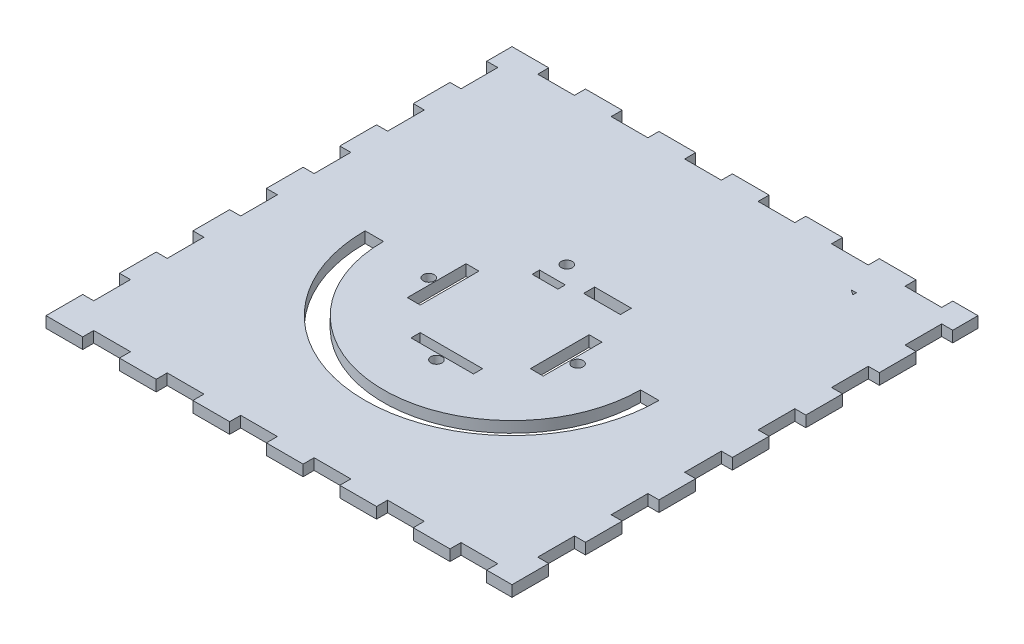
SolidWorks part; units mm, degrees
ref_plane "Front Plane" through (0, 0, 0) normal (0, 0, 1) x (1, 0, 0)
ref_plane "Top Plane" through (0, 0, 0) normal (0, 1, 0) x (1, 0, 0)
ref_plane "Right Plane" through (0, 0, 0) normal (1, 0, 0) x (0, 0, -1)
sketch "Sketch2" plane through (0, 0, 0) normal (0, 1, 0) x (1, 0, 0)
  line L1 (63.4385, 63.4385) -> (63.4385, -63.4385)
  line L2 (63.4385, -63.4385) -> (-63.4385, -63.4385)
  line L3 (-63.4385, -63.4385) -> (-63.4385, 63.4385)
  line L4 (-63.4385, 63.4385) -> (63.4385, 63.4385)
extrude "Boss-Extrude1" add sketch "Sketch2" along normal blind 3
sketch "Sketch3" plane through (0, 3, 0) normal (0, 1, 0) x (1, 0, 0)
  line L0 (-40, 0) -> (-35, 0) construction
  line L1 (-40, 0) -> (-35, 0)
  line L2 (35, 0) -> (40, 0)
  line L3 (35, 0) -> (40, 0) construction
  arc A0 (-35, 0) -> (35, 0) centre (0, 0) ccw
  arc A1 (-40, 0) -> (40, 0) centre (0, 0) ccw
  dimension "D1" = 70
  dimension "D2" = 5
extrude "Cut-Extrude1" cut sketch "Sketch3" against normal blind 10
sketch "Sketch4" plane through (0, 3, 0) normal (0, 1, 0) x (1, 0, 0)
  line L0 (40.0881, 52.2708) -> (41.4917, 51.3058)
  line L1 (40.0881, 52.2708) -> (41.4917, 52.2708)
  line L2 (41.4917, 52.2708) -> (41.4917, 51.3058)
extrude "Cut-Extrude2" cut sketch "Sketch4" against normal through all
sketch "Sketch5" plane through (0, 3, 0) normal (0, 1, 0) x (1, 0, 0)
  line L0 (-65.3757, 0) -> (63.4385, 0) construction
  line L1 (63.4385, -63.4385) -> (63.4385, 63.4385) construction
  line L2 (0, 63.4385) -> (0, -63.4385) construction
  line L3 (63.4385, 63.4385) -> (-63.4385, 63.4385) construction
  line L4 (-63.4385, -63.4385) -> (63.4385, -63.4385) construction
  line L5 (15, 6) -> (15, -10)
  line L10 (9.5, 18) -> (-8.5, 18) construction
  line L11 (-7, 14.5) -> (0, 14.5)
  line L12 (-8.5, -16.5) -> (8.5, -16.5)
  line L13 (-8.5, -16.5) -> (-8.5, -19)
  line L14 (-8.5, -19) -> (8.5, -19)
  line L15 (8.5, -16.5) -> (8.5, -19)
  line L16 (-18.5, 6) -> (-15, 6)
  line L17 (-18.5, 6) -> (-18.5, -10)
  line L18 (-18.5, -10) -> (-15, -10)
  line L19 (-15, 6) -> (-15, -10)
  line L20 (18.5, -10) -> (15, -10)
  line L21 (18.5, 6) -> (18.5, -10)
  line L22 (18.5, 6) -> (15, 6)
  line L23 (-7, 14.5) -> (-7, 12.5)
  line L28 (4.5, 18) -> (14.5, 18)
  line L29 (4.5, 18) -> (4.5, 15)
  line L30 (4.5, 15) -> (14.5, 15)
  line L31 (14.5, 18) -> (14.5, 15)
  line L32 (-7, 12.5) -> (0, 12.5)
  line L33 (0, 14.5) -> (0, 12.5)
  circle A0 centre (0.1281, -20.7) radius 1.5
  circle A1 centre (-4.5818, 19.5) radius 1.5
  circle A2 centre (-20.25, -2.4013) radius 1.5
  circle A3 centre (20.25, -2.4013) radius 1.5
  point P10 (0, 0)
  point P20 (0, -16.5)
  dimension "D11" = 3
  dimension "D12" = 3
  dimension "D17" = 3
  dimension "D2" = 7
  dimension "D3" = 17
  dimension "D4" = 2.5
  dimension "D5" = 2
  dimension "D6" = 3.5
  dimension "D7" = 16
  dimension "D8" = 6.5
  dimension "D9" = 4.5
  dimension "D10" = 0.5
  dimension "D13" = 1.5
  dimension "D14" = 1.7
  dimension "D15" = 10
  dimension "D16" = 3
  dimension "D18" = 1.75
extrude "Cut-Extrude3" cut sketch "Sketch5" against normal through all
sketch "Sketch6" plane through (0, 3, 0) normal (0, 1, 0) x (1, 0, 0)
  line L0 (-63.4385, 63.4385) -> (-63.4385, -63.4385) construction
  line L1 (-63.4385, -43.4385) -> (-60.4385, -43.4385)
  line L2 (-63.4385, -43.4385) -> (-63.4385, -53.4385)
  line L3 (-63.4385, -53.4385) -> (-60.4385, -53.4385)
  line L4 (-60.4385, -43.4385) -> (-60.4385, -53.4385)
  line L5 (-63.4385, -63.4385) -> (63.4385, -63.4385) construction
  line L6 (-63.4385, -23.4385) -> (-60.4385, -23.4385)
  line L7 (-63.4385, -23.4385) -> (-63.4385, -33.4385)
  line L8 (-63.4385, -33.4385) -> (-60.4385, -33.4385)
  line L9 (-60.4385, -23.4385) -> (-60.4385, -33.4385)
  line L10 (-63.4385, -3.4385) -> (-60.4385, -3.4385)
  line L11 (-63.4385, -3.4385) -> (-63.4385, -13.4385)
  line L12 (-63.4385, -13.4385) -> (-60.4385, -13.4385)
  line L13 (-60.4385, -3.4385) -> (-60.4385, -13.4385)
  line L14 (-63.4385, 16.5615) -> (-60.4385, 16.5615)
  line L15 (-63.4385, 16.5615) -> (-63.4385, 6.5615)
  line L16 (-63.4385, 6.5615) -> (-60.4385, 6.5615)
  line L17 (-60.4385, 16.5615) -> (-60.4385, 6.5615)
  line L18 (-63.4385, 36.5615) -> (-60.4385, 36.5615)
  line L19 (-63.4385, 36.5615) -> (-63.4385, 26.5615)
  line L20 (-63.4385, 26.5615) -> (-60.4385, 26.5615)
  line L21 (-60.4385, 36.5615) -> (-60.4385, 26.5615)
  line L22 (-63.4385, 56.5615) -> (-60.4385, 56.5615)
  line L23 (-63.4385, 56.5615) -> (-63.4385, 46.5615)
  line L24 (-63.4385, 46.5615) -> (-60.4385, 46.5615)
  line L25 (-60.4385, 56.5615) -> (-60.4385, 46.5615)
  line L26 (0, 63.4385) -> (0, -63.4385) construction
  line L27 (63.4385, 63.4385) -> (-63.4385, 63.4385) construction
  line L28 (60.4385, 56.5615) -> (60.4385, 46.5615)
  line L29 (63.4385, 46.5615) -> (60.4385, 46.5615)
  line L30 (63.4385, 56.5615) -> (63.4385, 46.5615)
  line L31 (63.4385, 56.5615) -> (60.4385, 56.5615)
  line L32 (60.4385, 36.5615) -> (60.4385, 26.5615)
  line L33 (63.4385, 26.5615) -> (60.4385, 26.5615)
  line L34 (63.4385, 36.5615) -> (63.4385, 26.5615)
  line L35 (63.4385, 36.5615) -> (60.4385, 36.5615)
  line L36 (60.4385, 16.5615) -> (60.4385, 6.5615)
  line L37 (63.4385, 6.5615) -> (60.4385, 6.5615)
  line L38 (63.4385, 16.5615) -> (63.4385, 6.5615)
  line L39 (63.4385, 16.5615) -> (60.4385, 16.5615)
  line L40 (60.4385, -3.4385) -> (60.4385, -13.4385)
  line L41 (63.4385, -13.4385) -> (60.4385, -13.4385)
  line L42 (63.4385, -3.4385) -> (63.4385, -13.4385)
  line L43 (63.4385, -3.4385) -> (60.4385, -3.4385)
  line L44 (60.4385, -23.4385) -> (60.4385, -33.4385)
  line L45 (63.4385, -33.4385) -> (60.4385, -33.4385)
  line L46 (63.4385, -23.4385) -> (63.4385, -33.4385)
  line L47 (63.4385, -23.4385) -> (60.4385, -23.4385)
  line L48 (60.4385, -43.4385) -> (60.4385, -53.4385)
  line L49 (63.4385, -53.4385) -> (60.4385, -53.4385)
  line L50 (63.4385, -43.4385) -> (63.4385, -53.4385)
  line L51 (63.4385, -43.4385) -> (60.4385, -43.4385)
  line L56 (-33.4385, -63.4385) -> (-23.4385, -63.4385)
  line L57 (-53.4385, -63.4385) -> (-43.4385, -63.4385)
  line L58 (-53.4385, -63.4385) -> (-53.4385, -60.4385)
  line L59 (-53.4385, -60.4385) -> (-43.4385, -60.4385)
  line L60 (-43.4385, -63.4385) -> (-43.4385, -60.4385)
  line L61 (-33.4385, -63.4385) -> (-33.4385, -60.4385)
  line L62 (-33.4385, -60.4385) -> (-23.4385, -60.4385)
  line L63 (-23.4385, -63.4385) -> (-23.4385, -60.4385)
  line L64 (-13.4385, -63.4385) -> (-3.4385, -63.4385)
  line L65 (-13.4385, -63.4385) -> (-13.4385, -60.4385)
  line L66 (-13.4385, -60.4385) -> (-3.4385, -60.4385)
  line L67 (-3.4385, -63.4385) -> (-3.4385, -60.4385)
  line L68 (6.5615, -63.4385) -> (16.5615, -63.4385)
  line L69 (6.5615, -63.4385) -> (6.5615, -60.4385)
  line L70 (6.5615, -60.4385) -> (16.5615, -60.4385)
  line L71 (16.5615, -63.4385) -> (16.5615, -60.4385)
  line L72 (26.5615, -63.4385) -> (36.5615, -63.4385)
  line L73 (26.5615, -63.4385) -> (26.5615, -60.4385)
  line L74 (26.5615, -60.4385) -> (36.5615, -60.4385)
  line L75 (36.5615, -63.4385) -> (36.5615, -60.4385)
  line L76 (46.5615, -63.4385) -> (56.5615, -63.4385)
  line L77 (46.5615, -63.4385) -> (46.5615, -60.4385)
  line L78 (46.5615, -60.4385) -> (56.5615, -60.4385)
  line L79 (56.5615, -63.4385) -> (56.5615, -60.4385)
  line L80 (-63.4385, 0) -> (63.4385, 0) construction
  line L81 (63.4385, -63.4385) -> (63.4385, 63.4385) construction
  line L82 (56.5615, 63.4385) -> (56.5615, 60.4385)
  line L83 (46.5615, 60.4385) -> (56.5615, 60.4385)
  line L84 (46.5615, 63.4385) -> (46.5615, 60.4385)
  line L85 (46.5615, 63.4385) -> (56.5615, 63.4385)
  line L86 (36.5615, 63.4385) -> (36.5615, 60.4385)
  line L87 (26.5615, 60.4385) -> (36.5615, 60.4385)
  line L88 (26.5615, 63.4385) -> (26.5615, 60.4385)
  line L89 (26.5615, 63.4385) -> (36.5615, 63.4385)
  line L90 (16.5615, 63.4385) -> (16.5615, 60.4385)
  line L91 (6.5615, 60.4385) -> (16.5615, 60.4385)
  line L92 (6.5615, 63.4385) -> (6.5615, 60.4385)
  line L93 (6.5615, 63.4385) -> (16.5615, 63.4385)
  line L94 (-3.4385, 63.4385) -> (-3.4385, 60.4385)
  line L95 (-13.4385, 60.4385) -> (-3.4385, 60.4385)
  line L96 (-13.4385, 63.4385) -> (-13.4385, 60.4385)
  line L97 (-13.4385, 63.4385) -> (-3.4385, 63.4385)
  line L98 (-23.4385, 63.4385) -> (-23.4385, 60.4385)
  line L99 (-33.4385, 60.4385) -> (-23.4385, 60.4385)
  line L100 (-33.4385, 63.4385) -> (-33.4385, 60.4385)
  line L101 (-43.4385, 63.4385) -> (-43.4385, 60.4385)
  line L102 (-53.4385, 60.4385) -> (-43.4385, 60.4385)
  line L103 (-53.4385, 63.4385) -> (-53.4385, 60.4385)
  line L104 (-53.4385, 63.4385) -> (-43.4385, 63.4385)
  line L105 (-33.4385, 63.4385) -> (-23.4385, 63.4385)
  dimension "D1" = 3
  dimension "D2" = 10
  dimension "D3" = 10
  dimension "D4" = 10
  dimension "D5" = 3
  dimension "D6" = 10
  dimension "D7" = 6
extrude "Cut-Extrude4" cut sketch "Sketch6" against normal through all
